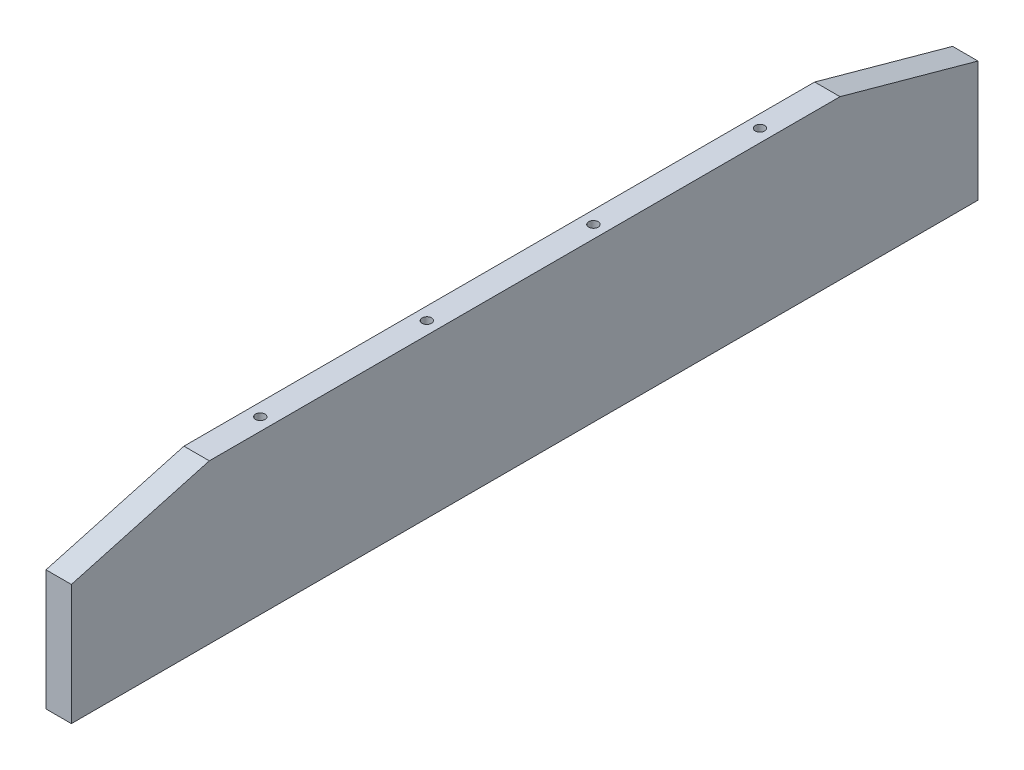
SolidWorks part; units mm, degrees
ref_plane "Front Plane" through (0, 0, 0) normal (0, 0, 1) x (1, 0, 0)
ref_plane "Top Plane" through (0, 0, 0) normal (0, 1, 0) x (1, 0, 0)
ref_plane "Right Plane" through (0, 0, 0) normal (1, 0, 0) x (0, 0, -1)
sketch "Sketch1" plane through (0, 0, 0) normal (1, 0, 0) x (0, 0, -1)
  line L0 (-37.279, 0) -> (248.465, 0)
  line L1 (248.465, 0) -> (248.465, 37.9953)
  line L2 (248.465, 37.9953) -> (204.9908, 50)
  line L3 (204.9908, 50) -> (6.1952, 50)
  line L4 (6.1952, 50) -> (-37.279, 37.9953)
  line L5 (-37.279, 37.9953) -> (-37.279, 0)
  line L7 (211.186, 50) -> (0, 50) construction
  line L8 (211.186, 50) -> (211.186, 0) construction
  line L9 (211.186, 0) -> (0, 0) construction
  line L10 (0, 50) -> (0, 0) construction
extrude "Boss-Extrude1" add sketch "Sketch1" along normal blind 8
sketch "Sketch6" plane through (0, 0, 0) normal (0, -1, 0) x (1, 0, 0)
  line L0 (4, 37.279) -> (4, -248.465) construction
  line L1 (8, 37.279) -> (0, 37.279) construction
  line L2 (8, -248.465) -> (0, -248.465) construction
  circle A0 centre (4, -26.25) radius 1.5
  circle A1 centre (4, -78.75) radius 1.5
  circle A2 centre (4, -131.25) radius 1.5
  circle A3 centre (4, -183.75) radius 1.5
extrude "Cut-Extrude2" cut sketch "Sketch6" against normal blind 50
